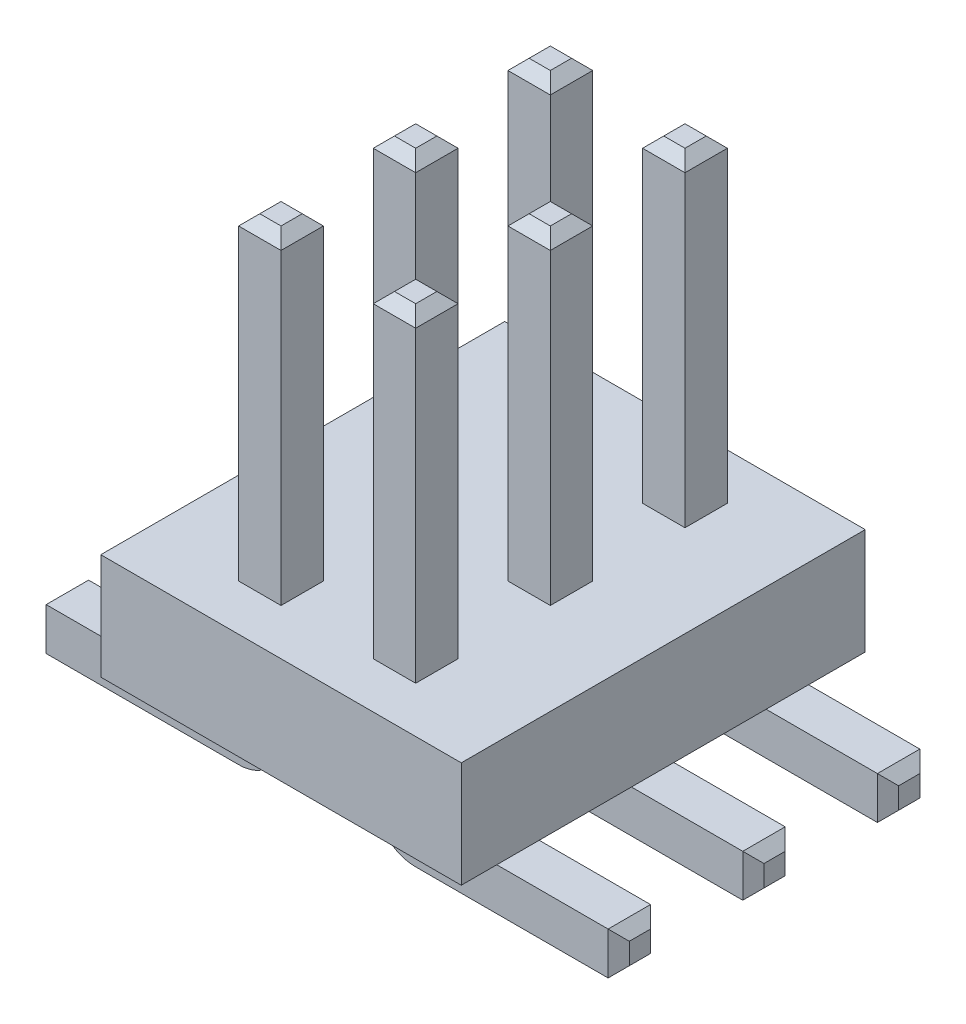
SolidWorks part; units mm, degrees
ref_plane "Vorne" through (0, 0, 0) normal (0, 0, 1) x (1, 0, 0)
ref_plane "Oben" through (0, 0, 0) normal (0, 1, 0) x (1, 0, 0)
ref_plane "Rechts" through (0, 0, 0) normal (1, 0, 0) x (0, 0, -1)
sketch "Skizze1" plane through (0, 0, 0) normal (0, 0, 1) x (1, 0, 0)
  line L1 (0, 0) -> (3.4, 0)
  line L2 (0, 0) -> (0, 1)
  line L3 (0, 1) -> (3.4, 1)
  line L4 (3.4, 0) -> (3.4, 1)
  dimension "D1" = 3.4
  dimension "D2" = 1
extrude "Aufsatz-Linear austragen1" add sketch "Skizze1" along normal blind 3.81
sketch "Skizze3" plane through (0, 0, 0) normal (0, -1, 0) x (1, 0, 0)
  line L2 (0, 3.81) -> (3.4, 3.81) construction
  line L3 (0.865, 2.975) -> (1.265, 2.975)
  line L4 (0.865, 2.975) -> (0.865, 3.375)
  line L5 (0.865, 3.375) -> (1.265, 3.375)
  line L6 (1.265, 2.975) -> (1.265, 3.375)
  line L7 (0.865, 2.975) -> (1.265, 3.375) construction
  line L8 (0.865, 3.375) -> (1.265, 2.975) construction
  line L9 (0, 3.81) -> (0, 0) construction
  line L10 (2.135, 2.975) -> (2.535, 2.975)
  line L11 (2.135, 2.975) -> (2.135, 3.375)
  line L12 (2.135, 3.375) -> (2.535, 3.375)
  line L13 (2.535, 2.975) -> (2.535, 3.375)
  line L14 (2.135, 2.975) -> (2.535, 3.375) construction
  line L15 (2.135, 3.375) -> (2.535, 2.975) construction
  line L16 (0.865, 1.705) -> (1.265, 1.705)
  line L17 (0.865, 1.705) -> (0.865, 2.105)
  line L18 (0.865, 2.105) -> (1.265, 2.105)
  line L19 (1.265, 1.705) -> (1.265, 2.105)
  line L20 (0.865, 1.705) -> (1.265, 2.105) construction
  line L21 (0.865, 2.105) -> (1.265, 1.705) construction
  line L22 (2.135, 1.705) -> (2.535, 1.705)
  line L23 (2.135, 1.705) -> (2.135, 2.105)
  line L24 (2.135, 2.105) -> (2.535, 2.105)
  line L25 (2.535, 1.705) -> (2.535, 2.105)
  line L26 (2.135, 1.705) -> (2.535, 2.105) construction
  line L27 (2.135, 2.105) -> (2.535, 1.705) construction
  line L28 (0.865, 0.435) -> (1.265, 0.435)
  line L29 (0.865, 0.435) -> (0.865, 0.835)
  line L30 (0.865, 0.835) -> (1.265, 0.835)
  line L31 (1.265, 0.435) -> (1.265, 0.835)
  line L32 (0.865, 0.435) -> (1.265, 0.835) construction
  line L33 (0.865, 0.835) -> (1.265, 0.435) construction
  line L34 (2.135, 0.435) -> (2.535, 0.435)
  line L35 (2.135, 0.435) -> (2.135, 0.835)
  line L36 (2.135, 0.835) -> (2.535, 0.835)
  line L37 (2.535, 0.435) -> (2.535, 0.835)
  line L38 (2.135, 0.435) -> (2.535, 0.835) construction
  line L39 (2.135, 0.835) -> (2.535, 0.435) construction
  point P0 (1.065, 3.175)
  point P12 (2.335, 3.175)
  point P17 (1.065, 1.905)
  point P22 (2.335, 1.905)
  point P27 (1.065, 0.635)
  point P32 (2.335, 0.635)
  dimension "D3" = 0.635
  dimension "D1" = 0.4
  dimension "D2" = 0.4
  dimension "D4" = 1.065
  dimension "D5" = 3
extrude "Aufsatz-Linear austragen3" add sketch "Skizze3" along normal blind 0.5
sketch "Skizze4" plane through (2.535, 0, 0) normal (1, 0, 0) x (0, 0, -1)
  line L0 (-2.975, -0.5) -> (-2.975, 0) construction
  line L1 (-3.375, -0.5) -> (-2.975, -0.5)
  line L2 (-3.375, -0.5) -> (-3.375, -0.1)
  line L3 (-3.375, -0.1) -> (-2.975, -0.1)
  line L4 (-2.975, -0.5) -> (-2.975, -0.1)
  line L5 (-1.705, -0.5) -> (-1.705, 0) construction
  line L6 (-2.105, -0.5) -> (-1.705, -0.5)
  line L7 (-2.105, -0.5) -> (-2.105, -0.1)
  line L8 (-2.105, -0.1) -> (-1.705, -0.1)
  line L9 (-1.705, -0.5) -> (-1.705, -0.1)
  line L10 (-0.435, -0.5) -> (-0.435, 0) construction
  line L11 (-0.835, -0.5) -> (-0.435, -0.5)
  line L12 (-0.835, -0.5) -> (-0.835, -0.1)
  line L13 (-0.835, -0.1) -> (-0.435, -0.1)
  line L14 (-0.435, -0.5) -> (-0.435, -0.1)
  dimension "D1" = 0.4
  dimension "D2" = 0.4
  dimension "D3" = 0.4
extrude "Aufsatz-Linear austragen4" add sketch "Skizze4" along normal blind 1.915
sketch "Skizze5" plane through (0.865, 0, 0) normal (-1, 0, 0) x (0, 0, 1)
  line L0 (1.705, -0.5) -> (1.705, 0) construction
  line L1 (3.375, -0.5) -> (2.975, -0.5)
  line L2 (3.375, -0.5) -> (3.375, -0.1)
  line L3 (3.375, -0.1) -> (2.975, -0.1)
  line L4 (2.975, -0.5) -> (2.975, -0.1)
  line L5 (2.105, -0.5) -> (1.705, -0.5)
  line L6 (2.105, -0.5) -> (2.105, -0.1)
  line L7 (2.105, -0.1) -> (1.705, -0.1)
  line L8 (1.705, -0.5) -> (1.705, -0.1)
  line L9 (0.435, -0.5) -> (0.435, 0) construction
  line L10 (0.835, -0.5) -> (0.435, -0.5)
  line L11 (0.835, -0.5) -> (0.835, -0.1)
  line L12 (0.835, -0.1) -> (0.435, -0.1)
  line L13 (0.435, -0.5) -> (0.435, -0.1)
extrude "Aufsatz-Linear austragen5" add sketch "Skizze5" along normal blind 1.915
sketch "Skizze6" plane through (0, 1, 0) normal (0, 1, 0) x (1, 0, 0)
  line L0 (3.4, 0) -> (0, 0) construction
  line L1 (0.865, -0.835) -> (1.265, -0.835)
  line L2 (0.865, -0.835) -> (0.865, -0.435)
  line L3 (0.865, -0.435) -> (1.265, -0.435)
  line L4 (1.265, -0.835) -> (1.265, -0.435)
  line L5 (0.865, -0.835) -> (1.265, -0.435) construction
  line L6 (0.865, -0.435) -> (1.265, -0.835) construction
  line L7 (0, -3.81) -> (0, 0) construction
  line L8 (2.135, -0.835) -> (2.535, -0.835)
  line L9 (2.135, -0.835) -> (2.135, -0.435)
  line L10 (2.135, -0.435) -> (2.535, -0.435)
  line L11 (2.535, -0.835) -> (2.535, -0.435)
  line L12 (2.135, -0.835) -> (2.535, -0.435) construction
  line L13 (2.135, -0.435) -> (2.535, -0.835) construction
  line L14 (0.865, -2.105) -> (1.265, -2.105)
  line L15 (0.865, -2.105) -> (0.865, -1.705)
  line L16 (0.865, -1.705) -> (1.265, -1.705)
  line L17 (1.265, -2.105) -> (1.265, -1.705)
  line L18 (0.865, -2.105) -> (1.265, -1.705) construction
  line L19 (0.865, -1.705) -> (1.265, -2.105) construction
  line L20 (2.135, -2.105) -> (2.535, -2.105)
  line L21 (2.135, -2.105) -> (2.135, -1.705)
  line L22 (2.135, -1.705) -> (2.535, -1.705)
  line L23 (2.535, -2.105) -> (2.535, -1.705)
  line L24 (2.135, -2.105) -> (2.535, -1.705) construction
  line L25 (2.135, -1.705) -> (2.535, -2.105) construction
  line L26 (0.865, -3.375) -> (1.265, -3.375)
  line L27 (0.865, -3.375) -> (0.865, -2.975)
  line L28 (0.865, -2.975) -> (1.265, -2.975)
  line L29 (1.265, -3.375) -> (1.265, -2.975)
  line L30 (0.865, -3.375) -> (1.265, -2.975) construction
  line L31 (0.865, -2.975) -> (1.265, -3.375) construction
  line L32 (2.135, -3.375) -> (2.535, -3.375)
  line L33 (2.135, -3.375) -> (2.135, -2.975)
  line L34 (2.135, -2.975) -> (2.535, -2.975)
  line L35 (2.535, -3.375) -> (2.535, -2.975)
  line L36 (2.135, -3.375) -> (2.535, -2.975) construction
  line L37 (2.135, -2.975) -> (2.535, -3.375) construction
  point P0 (1.065, -0.635)
  point P11 (2.335, -0.635)
  point P16 (1.065, -1.905)
  point P21 (2.335, -1.905)
  point P26 (1.065, -3.175)
  point P31 (2.335, -3.175)
  dimension "D1" = 0.4
  dimension "D2" = 0.4
  dimension "D3" = 0.635
  dimension "D4" = 1.065
  dimension "D5" = 3
extrude "Aufsatz-Linear austragen6" add sketch "Skizze6" along normal blind 3
chamfer "Fase2" distance 0.1 angle 45 48 edges at (-1.05, -0.1, 3.175) (-1.05, -0.3, 3.375) (-1.05, -0.5, 3.175) (-1.05, -0.3, 2.975) (-1.05, -0.1, 1.905) (-1.05, -0.3, 2.105) (-1.05, -0.5, 1.905) (-1.05, -0.3, 1.705) (-1.05, -0.1, 0.635) (-1.05, -0.3, 0.835) (-1.05, -0.5, 0.635) (-1.05, -0.3, 0.435) (4.45, -0.3, 0.835) (4.45, -0.1, 0.635) (4.45, -0.3, 0.435) (4.45, -0.5, 0.635) (4.45, -0.3, 1.705) (4.45, -0.5, 1.905) (4.45, -0.3, 2.105) (4.45, -0.1, 1.905) (4.45, -0.3, 3.375) (4.45, -0.1, 3.175) (4.45, -0.5, 3.175) (4.45, -0.3, 2.975) (1.265, 4, 3.175) (1.065, 4, 3.375) (0.865, 4, 3.175) (1.065, 4, 2.975) (2.535, 4, 1.905) (2.335, 4, 2.105) (2.135, 4, 1.905) (2.335, 4, 1.705) (2.335, 4, 0.835) (2.535, 4, 0.635) (2.335, 4, 0.435) (2.135, 4, 0.635) (1.065, 4, 0.835) (1.265, 4, 0.635) (1.065, 4, 0.435) (0.865, 4, 0.635) (1.065, 4, 1.705) (0.865, 4, 1.905) (1.065, 4, 2.105) (1.265, 4, 1.905) (2.335, 4, 2.975) (2.135, 4, 3.175) (2.335, 4, 3.375) (2.535, 4, 3.175)
fillet "Verrundung1" radius 0.1 6 edges at (0.865, -0.1, 3.175) (0.865, -0.1, 1.905) (0.865, -0.1, 0.635) (2.535, -0.1, 3.175) (2.535, -0.1, 1.905) (2.535, -0.1, 0.635)
fillet "Verrundung2" radius 0.4 6 edges at (1.265, -0.5, 3.175) (2.135, -0.5, 3.175) (1.265, -0.5, 1.905) (2.135, -0.5, 1.905) (2.135, -0.5, 0.635) (1.265, -0.5, 0.635)
